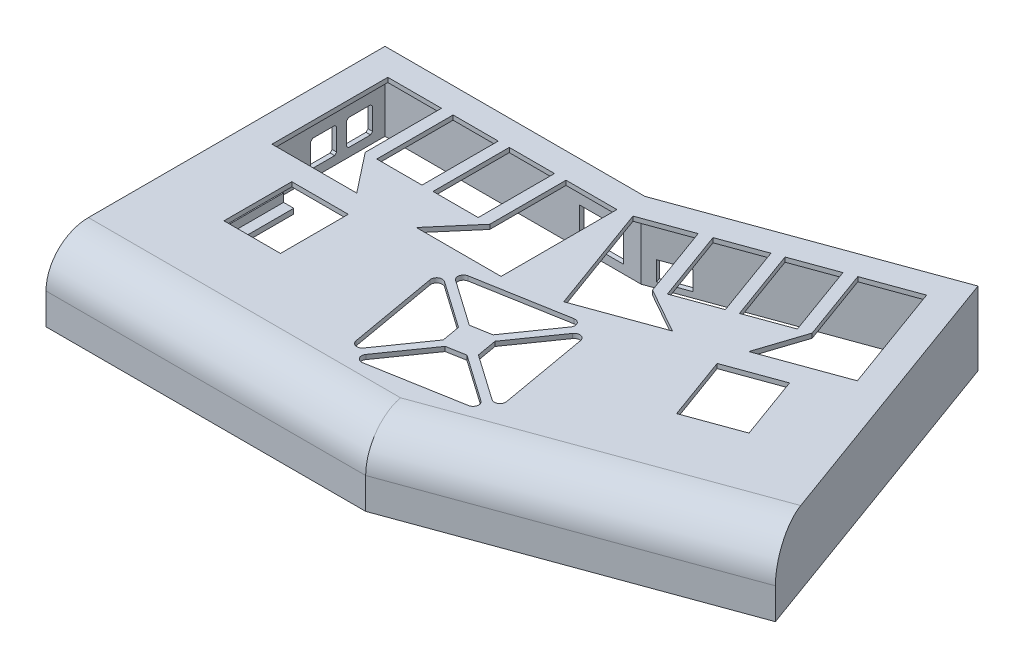
SolidWorks part; units mm, degrees
ref_plane "Front Plane" through (0, 0, 0) normal (0, 0, 1) x (1, 0, 0)
ref_plane "Top Plane" through (0, 0, 0) normal (0, 1, 0) x (1, 0, 0)
ref_plane "Right Plane" through (0, 0, 0) normal (1, 0, 0) x (0, 0, -1)
sketch "Sketch1" plane through (0, 0, 0) normal (0, 1, 0) x (1, 0, 0)
  line L0 (0, 0) -> (0, 152.4)
  line L1 (0, 152.4) -> (116.84, 152.4)
  line L2 (116.84, 152.4) -> (143.7122, 0)
  line L3 (0, 0) -> (143.7122, 0)
  dimension "D1" = 152.4
  dimension "D2" = 116.84
  dimension "D3" = 100
extrude "Boss-Extrude1" add sketch "Sketch1" along normal blind 33.02 contours L2 L3 L0 L1
fillet "Fillet1" radius 19.05 1 edges at (71.8561, 33.02, 0)
mirror "Mirror6" about plane through (116.84, 33.02, -152.4) normal (0.9848, 0, -0.1736) of bodies 101
shell "Shell3" thickness 2.032 removed face at (127.6572, 0, -91.0524)
sketch "Sketch7" plane through (0, 33.02, 0) normal (0, 1, 0) x (1, 0, 0)
  line L0 (12.7, 152.4) -> (12.7, 88.9) construction
  line L1 (0, 152.4) -> (116.84, 152.4) construction
  line L2 (0, 19.05) -> (0, 152.4) construction
  line L3 (0, 88.9) -> (61.5318, 88.9) construction
  dimension "D1" = 12.7
  dimension "D2" = 63.5
sketch "Sketch9" plane through (0, 33.02, 0) normal (0, 1, 0) x (1, 0, 0)
  line L0 (0, 78.74) -> (62.1493, 78.74) construction
  line L1 (0, 19.05) -> (0, 152.4) construction
  line L2 (0, 88.9) -> (61.5318, 88.9) construction
  line L3 (31.75, 78.74) -> (31.75, 42.1216) construction
  line L4 (116.84, 152.4) -> (140.3532, 19.05) construction
  line L5 (31.75, 78.74) -> (57.15, 78.74)
  line L6 (31.75, 78.74) -> (31.75, 48.26)
  line L7 (31.75, 48.26) -> (57.15, 48.26)
  line L8 (57.15, 78.74) -> (57.15, 48.26)
  line L9 (198.1235, 103.5974) -> (208.5482, 74.9556)
  line L10 (232.4164, 83.6429) -> (208.5482, 74.9556)
  line L11 (221.9916, 112.2847) -> (232.4164, 83.6429)
  line L12 (221.9916, 112.2847) -> (198.1235, 103.5974)
  dimension "D1" = 10.16
  dimension "D2" = 31.75
  dimension "D3" = 25.4
  dimension "D4" = 30.48
extrude "Cut-Extrude6" cut sketch "Sketch9" against normal blind 5.08 contours L9 L10 L11 L12 | L6 L5 L8 L7
sketch "Sketch16" plane through (0, 0, 0) normal (-1, 0, 0) x (0, 0, 1)
  line L0 (-81.28, 33.02) -> (-151.6588, 21.2426) construction
  line L1 (-19.05, 33.02) -> (-152.4, 33.02) construction
  line L2 (-81.28, 33.02) -> (-152.4, 33.02) construction
  dimension "D1" = 9.5
  dimension "D2" = 71.12
sketch "Sketch8" plane through (0, 33.02, 0) normal (0, 1, 0) x (1, 0, 0)
  line L0 (12.7, 88.9) -> (31.3923, 88.9)
  line L1 (12.7, 88.9) -> (12.7, 140.97)
  line L2 (12.7, 140.97) -> (36.83, 140.97)
  line L3 (42.0378, 106.68) -> (42.0378, 140.97)
  line L4 (97.9095, 88.9) -> (115.6895, 88.9)
  line L5 (115.6895, 88.9) -> (115.6895, 140.97)
  line L6 (87.6217, 106.68) -> (87.6217, 140.97)
  line L7 (36.83, 140.97) -> (36.83, 106.68)
  line L8 (50.8, 128.016) -> (50.8, 88.9) construction
  line L9 (50.8, 88.9) -> (31.3923, 88.9)
  line L10 (77.5895, 128.016) -> (77.5895, 88.9) construction
  line L11 (77.5895, 88.9) -> (97.9095, 88.9)
  line L12 (36.83, 106.68) -> (50.8, 88.9)
  line L13 (115.6895, 140.97) -> (92.8295, 140.97)
  line L14 (92.8295, 140.97) -> (92.8295, 106.68)
  line L15 (92.8295, 106.68) -> (77.5895, 88.9)
  line L16 (42.0378, 140.97) -> (62.3578, 140.97)
  line L17 (62.3578, 140.97) -> (62.3578, 106.68)
  line L18 (62.3578, 106.68) -> (42.0378, 106.68)
  line L19 (87.6217, 140.97) -> (67.3017, 140.97)
  line L20 (67.3017, 140.97) -> (67.3017, 106.68)
  line L21 (67.3017, 106.68) -> (87.6217, 106.68)
  line L22 (116.84, 152.4) -> (140.3532, 19.05)
  line L23 (162.0632, 142.911) -> (175.4416, 106.154) construction
  line L24 (187.2371, 152.0736) -> (200.6156, 115.3166) construction
  line L25 (179.0279, 126.3804) -> (159.9333, 119.4305)
  line L26 (167.3, 158.6024) -> (179.0279, 126.3804)
  line L27 (148.2055, 151.6526) -> (167.3, 158.6024)
  line L28 (183.6737, 128.0713) -> (202.7682, 135.0211)
  line L29 (171.9458, 160.2933) -> (183.6737, 128.0713)
  line L30 (191.0403, 167.2432) -> (171.9458, 160.2933)
  line L31 (155.0396, 117.6493) -> (175.4416, 106.154)
  line L32 (143.3117, 149.8714) -> (155.0396, 117.6493)
  line L33 (121.8304, 142.0528) -> (143.3117, 149.8714)
  line L34 (207.662, 136.8023) -> (200.6156, 115.3166)
  line L35 (175.4416, 106.154) -> (156.3471, 99.2041)
  line L36 (200.6156, 115.3166) -> (218.8529, 121.9544)
  line L37 (195.9341, 169.0244) -> (207.662, 136.8023)
  line L38 (159.9333, 119.4305) -> (148.2055, 151.6526)
  line L39 (139.6393, 93.123) -> (121.8304, 142.0528)
  line L40 (156.3471, 99.2041) -> (139.6393, 93.123)
  line L41 (202.7682, 135.0211) -> (191.0403, 167.2432)
  line L42 (218.6089, 177.2773) -> (195.9341, 169.0244)
  line L43 (236.4179, 128.3475) -> (218.6089, 177.2773)
  line L44 (236.4179, 128.3475) -> (218.8529, 121.9544)
  point P0 (22.6758, 121.8699)
  point P6 (50.9318, 131.9996)
  point P10 (106.7995, 121.758)
  point P17 (78.7317, 132.0383)
  point P52 (159.6142, 146.3)
  point P53 (136.7551, 127.04)
  point P54 (185.7508, 155.7718)
  point P55 (215.7673, 155.9171)
extrude "Cut-Extrude5" cut sketch "Sketch8" against normal blind 5.08 contours L12 L7 L2 L1 L0 L9 | L18 L17 L16 L3 | L20 L21 L6 L19 | L14 L15 L11 L4 L5 L13 | L40 L35 L31 L32 L33 L39 | L38 L25 L26 L27 | L28 L41 L30 L29 | L44 L43 L42 L37 L34 L36 region at (26.2692, 33.02, -113.1262) region at (52.1978, 33.02, -123.825) region at (102.5724, 33.02, -112.8802) region at (77.4617, 33.02, -123.825) region at (163.6167, 33.02, -139.0165) region at (187.357, 33.02, -147.6572) region at (143.7637, 33.02, -120.1433) region at (215.3812, 33.02, -146.4718)
sketch "Sketch17" plane through (0, 0, 0) normal (-1, 0, 0) x (0, 0, 1)
  line L0 (-152.4, 3.81) -> (-96.647, 3.81) construction
  line L1 (-152.4, 33.02) -> (-152.4, 0) construction
  line L2 (0, 0) -> (-152.4, 0) construction
  line L3 (-116.967, 9.652) -> (-83.185, 9.652) construction
  line L4 (-144.78, 3.81) -> (-144.78, 18.0081) construction
  line L5 (-152.4, 33.02) -> (-152.4, 0) construction
  line L6 (-128.651, 3.81) -> (-128.651, 15.494) construction
  line L7 (-144.78, 3.81) -> (-133.096, 3.81)
  line L8 (-144.78, 3.81) -> (-144.78, 15.494)
  line L9 (-144.78, 15.494) -> (-133.096, 15.494)
  line L10 (-133.096, 3.81) -> (-133.096, 15.494)
  line L11 (-96.647, 3.81) -> (-96.647, 15.494) construction
  line L12 (-128.651, 3.81) -> (-116.967, 3.81)
  line L13 (-128.651, 3.81) -> (-128.651, 15.494)
  line L14 (-128.651, 15.494) -> (-116.967, 15.494)
  line L15 (-116.967, 3.81) -> (-116.967, 15.494)
  line L16 (-143.8723, 15.494) -> (-144.78, 14.5863)
  line L17 (-96.647, 8.89) -> (-69.723, 8.89)
  line L18 (-96.647, 8.89) -> (-96.647, 10.414)
  line L19 (-96.647, 10.414) -> (-69.723, 10.414)
  line L20 (-69.723, 8.89) -> (-69.723, 10.414)
  line L21 (-96.647, 8.89) -> (-69.723, 10.414) construction
  line L22 (-96.647, 10.414) -> (-69.723, 8.89) construction
  line L23 (-134.0037, 15.494) -> (-133.096, 14.5863)
  line L24 (-133.096, 4.7177) -> (-134.0037, 3.81)
  line L25 (-144.78, 4.7177) -> (-143.8723, 3.81)
  line L26 (-143.8723, 15.494) -> (-134.0037, 15.494)
  line L27 (-127.7433, 15.494) -> (-128.651, 14.5863)
  line L28 (-128.651, 4.7177) -> (-127.7433, 3.81)
  line L29 (-117.8747, 15.494) -> (-116.967, 14.5863)
  line L30 (-116.967, 4.7177) -> (-117.8747, 3.81)
  line L31 (-133.096, 14.5863) -> (-133.096, 4.7177)
  line L32 (-134.0037, 3.81) -> (-143.8723, 3.81)
  line L33 (-144.78, 4.7177) -> (-144.78, 14.5863)
  line L34 (-127.7433, 15.494) -> (-117.8747, 15.494)
  line L35 (-116.967, 14.5863) -> (-116.967, 4.7177)
  line L36 (-117.8747, 3.81) -> (-127.7433, 3.81)
  line L37 (-128.651, 4.7177) -> (-128.651, 14.5863)
  dimension "D1" = 3.81
  dimension "D2" = 7.62
  dimension "D3" = 11.684
  dimension "D4" = 11.684
  dimension "D5" = 4.445
  dimension "D6" = 11.684
  dimension "D7" = 20.32
  dimension "D8" = 33.782
  dimension "D9" = 1.524
  dimension "D10" = 26.924
  dimension "D11" = 45
  dimension "D12" = 45
  dimension "D13" = 45
  dimension "D14" = 45
  dimension "D15" = 45
  dimension "D16" = 45
  dimension "D17" = 45
  dimension "D18" = 45
  dimension "D19" = 1.2837
extrude "Cut-Extrude7" cut sketch "Sketch17" against normal blind 2.54 contours L8 L25 L7 L24 L10 L23 L9 L16 | L30 L15 L29 L14 L27 L13 L28 L12 | L17 L20 L19 L18 region at (0, 9.652, -138.938) region at (0, 9.652, -122.809) region at (0, 9.652, -83.185)
sketch "Sketch18" plane through (0, 0, 0) normal (-1, 0, 0) x (0, 0, 1)
  line L0 (-83.185, 10.414) -> (-83.185, 8.89) construction
  line L1 (-96.647, 10.414) -> (-69.723, 10.414) construction
  line L2 (-96.647, 8.89) -> (-69.723, 8.89) construction
  line L4 (-96.647, 5.207) -> (-69.723, 5.207)
  line L5 (-96.647, 5.207) -> (-96.647, 14.097)
  line L6 (-96.647, 14.097) -> (-69.723, 14.097)
  line L7 (-69.723, 5.207) -> (-69.723, 14.097)
  line L8 (-96.647, 5.207) -> (-69.723, 14.097) construction
  line L9 (-96.647, 14.097) -> (-69.723, 5.207) construction
  point P6 (-83.185, 9.652)
  dimension "D1" = 26.924
  dimension "D2" = 8.89
extrude "Boss-Extrude2" add sketch "Sketch18" against normal blind 10.16 contours L5 L4 L7 L6
sketch "Sketch20" plane through (10.16, 0, 0) normal (1, 0, 0) x (0, 0, -1)
  line L0 (69.723, 9.652) -> (96.647, 9.652) construction
  line L1 (69.723, 5.207) -> (69.723, 14.097) construction
  line L2 (96.647, 5.207) -> (96.647, 14.097) construction
  line L4 (69.723, 8.89) -> (96.647, 8.89)
  line L5 (69.723, 8.89) -> (69.723, 10.414)
  line L6 (69.723, 10.414) -> (96.647, 10.414)
  line L7 (96.647, 8.89) -> (96.647, 10.414)
  line L8 (69.723, 8.89) -> (96.647, 10.414) construction
  line L9 (69.723, 10.414) -> (96.647, 8.89) construction
  point P6 (83.185, 9.652)
  dimension "D1" = 1.524
extrude "Cut-Extrude8" cut sketch "Sketch20" against normal blind 10.16
sketch "Sketch21" plane through (2.032, 0, 0) normal (1, 0, 0) x (0, 0, -1)
  line L5 (96.647, 5.207) -> (40.767, 5.207)
  line L6 (96.647, 5.207) -> (96.647, 2.921)
  line L7 (96.647, 2.921) -> (40.767, 2.921)
  line L8 (40.767, 5.207) -> (40.767, 2.921)
  dimension "D1" = 55.88
  dimension "D2" = 2.286
extrude "Boss-Extrude3" add sketch "Sketch21" along normal blind 12.7
sketch "Sketch23" plane through (0, 0, -152.4) normal (0, 0, -1) x (-1, 0, 0)
  line L0 (-109.22, 0) -> (-109.22, 18.4369) construction
  line L1 (0, 0) -> (-116.84, 0) construction
  line L2 (-116.84, 33.02) -> (-116.84, 0) construction
  dimension "D1" = 7.62
sketch "Sketch24" plane through (0, 0, -152.4) normal (0, 0, -1) x (-1, 0, 0)
  line L0 (-109.22, 3.81) -> (-87.289, 3.81) construction
  line L1 (-109.22, 0) -> (-109.22, 18.4369) construction
  line L2 (0, 0) -> (-116.84, 0) construction
  line L3 (-116.84, 33.02) -> (-116.84, 0) construction
  line L4 (-109.22, 3.81) -> (-89.408, 3.81)
  line L5 (-109.22, 3.81) -> (-109.22, 17.018)
  line L6 (-109.22, 17.018) -> (-89.408, 17.018)
  line L7 (-89.408, 3.81) -> (-89.408, 17.018)
  dimension "D1" = 3.81
  dimension "D2" = 19.812
  dimension "D3" = 13.208
  dimension "D4" = 7.62
extrude "ON/OFF" cut sketch "Sketch24" against normal blind 12.7 contours L5 L4 L7 L6
sketch "Sketch27" plane through (-35.3127, 0, -97.0209) normal (-0.342, 0, -0.9397) x (-0.9397, 0, 0.342)
  line L0 (-161.9176, 2.54) -> (-192.9577, 2.54) construction
  line L1 (-161.9176, 33.02) -> (-161.9176, 0) construction
  line L2 (-278.7576, 0) -> (-161.9176, 0) construction
  line L3 (-166.9976, 2.54) -> (-166.9976, 24.7573) construction
  line L5 (-166.9976, 2.54) -> (-179.6976, 2.54)
  line L6 (-166.9976, 2.54) -> (-166.9976, 11.176)
  line L7 (-166.9976, 11.176) -> (-179.6976, 11.176)
  line L8 (-179.6976, 2.54) -> (-179.6976, 11.176)
  dimension "D1" = 2.54
  dimension "D2" = 5.08
  dimension "D3" = 8.636
  dimension "D4" = 12.7
sketch "Sketch26" plane through (0, 33.02, 0) normal (0, 1, 0) x (1, 0, 0)
  line L0 (109.1967, 25.1769) -> (127.4198, 51.2022)
  line L1 (116.84, 152.4) -> (116.84, 19.05) construction
  line L2 (0, 19.05) -> (140.3532, 19.05) construction
  line L3 (116.84, 152.4) -> (162.4484, 27.092) construction
  line L4 (272.2421, 67.0536) -> (140.3532, 19.05) construction
  line L5 (128.2595, 85.2802) -> (157.0257, 90.3525) construction
  line L6 (157.0257, 90.3525) -> (99.4933, 80.208) construction
  line L10 (99.4933, 80.208) -> (157.0257, 90.3525)
  line L11 (99.4933, 80.208) -> (109.6378, 22.6755)
  line L12 (157.0257, 90.3525) -> (167.1703, 32.82)
  line L13 (109.6378, 22.6755) -> (167.1703, 32.82)
  line L14 (101.9947, 80.649) -> (112.1392, 23.1166) construction
  line L15 (99.9343, 77.7065) -> (157.4668, 87.8511) construction
  line L16 (154.5243, 89.9114) -> (164.6689, 32.379) construction
  line L17 (166.7292, 35.3214) -> (109.1967, 25.1769) construction
  line L18 (128.2595, 85.2802) -> (138.7411, 28.1925) construction
  line L19 (99.9343, 77.7065) -> (125.9596, 59.4834)
  line L20 (112.1392, 23.1166) -> (130.3503, 49.1246)
  line L25 (157.4668, 87.8511) -> (139.5756, 62.2998)
  line L26 (101.9947, 80.649) -> (127.5459, 62.7579)
  line L27 (154.5243, 89.9114) -> (136.6332, 64.3602)
  line L28 (164.6689, 32.379) -> (138.6608, 50.59)
  line L29 (166.7292, 35.3214) -> (141.178, 53.2126)
  line L30 (127.5459, 62.7579) -> (136.6332, 64.3602)
  line L31 (139.5756, 62.2998) -> (141.178, 53.2126)
  line L32 (138.6608, 50.59) -> (130.3503, 49.1246)
  line L33 (127.4198, 51.2022) -> (125.9596, 59.4834)
  line L34 (99.9343, 77.7065) -> (109.1967, 25.1769)
  line L35 (112.1392, 23.1166) -> (164.6689, 32.379)
  line L36 (166.7292, 35.3214) -> (157.4668, 87.8511)
  line L37 (154.5243, 89.9114) -> (101.9947, 80.649)
  line L38 (116.84, 152.4) -> (133.5003, 56.7364) construction
  dimension "D1" = 58.42
  dimension "D2" = 29.21
  dimension "D3" = 58.42
  dimension "D4" = 2.54
  dimension "D5" = 2.54
  dimension "D6" = 2.54
  dimension "D7" = 2.54
  dimension "D8" = 45
  dimension "D9" = 45
  dimension "D10" = 45
  dimension "D11" = 45
  dimension "D12" = 45
  dimension "D13" = 45
  dimension "D14" = 45
  dimension "D15" = 45
  dimension "D16" = 97.1035
extrude "Cut-Extrude12" cut sketch "Sketch27" against normal blind 12.7
extrude "D Pad" cut sketch "Sketch26" against normal blind 12.7 contours L26 L30 L27 L10 | L0 L33 L19 L11 | L28 L32 L20 L13 | L25 L31 L29 L12 region at (112.9446, 33.02, -52.9192) region at (136.927, 33.02, -36.1243) region at (129.7245, 33.02, -76.972) region at (153.7898, 33.02, -60.1213)
fillet "D Pad Fillet" radius 2.54 8 edges at (101.9947, 32.004, -80.649) (154.5243, 32.004, -89.9114) (99.9343, 32.004, -77.7065) (109.1967, 32.004, -25.1769) (112.1392, 32.004, -23.1166) (164.6689, 32.004, -32.379) (166.7292, 32.004, -35.3214) (157.4668, 32.004, -87.8511)
sketch "Sketch29" plane through (2.032, 0, 0) normal (1, 0, 0) x (0, 0, -1)
  line L1 (69.723, 14.097) -> (66.167, 14.097)
  line L2 (69.723, 14.097) -> (69.723, 5.207)
  line L3 (69.723, 5.207) -> (66.167, 5.207)
  line L4 (66.167, 14.097) -> (66.167, 5.207)
  dimension "D1" = 3.556
  dimension "D2" = 8.89
extrude "SliderEXT1" add sketch "Sketch29" along normal blind 8.128
sketch "Sketch30" plane through (10.16, 0, 0) normal (1, 0, 0) x (0, 0, -1)
  line L0 (66.167, 14.097) -> (66.167, 5.207) construction
  line L1 (69.723, 10.414) -> (66.167, 10.414)
  line L2 (69.723, 10.414) -> (69.723, 8.89)
  line L3 (69.723, 8.89) -> (66.167, 8.89)
  line L4 (66.167, 10.414) -> (66.167, 8.89)
  dimension "D1" = 1.524
extrude "SliderEXT2" cut sketch "Sketch30" against normal blind 10.16
